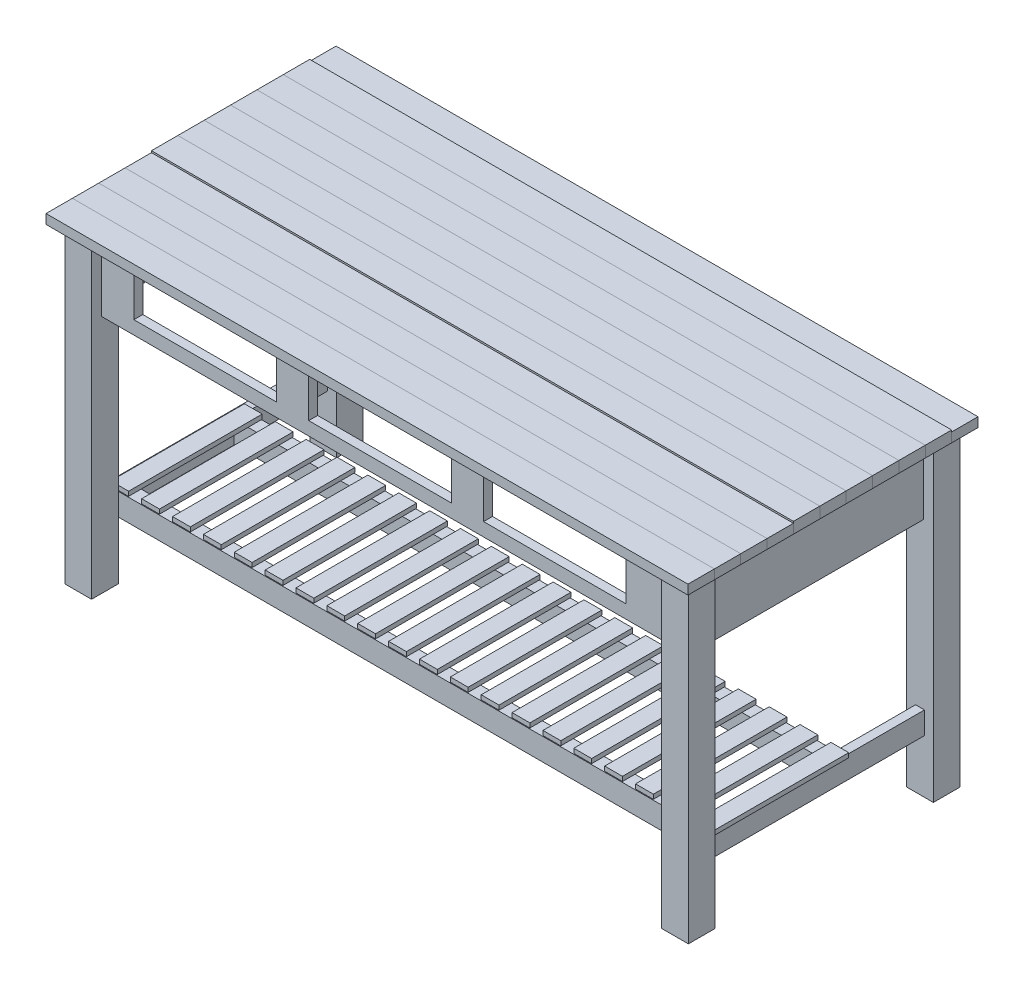
SolidWorks part; units mm, degrees
ref_plane "Default Plane" through (914.4, 26.9875, 137.455) normal (0, -1, 0) x (-1, 0, 0)
sketch3d "Bounding-Box_Cut-List-Item1"
  line L0 (0, 75.184, 0) -> (1830.3875, 75.184, 0) construction
  line L1 (1830.3875, 75.184, 0) -> (1830.3875, 0, 0) construction
  line L2 (1830.3875, 0, 0) -> (0, 0, 0) construction
  line L3 (0, 0, 0) -> (0, 75.184, 0) construction
  line L4 (0, 75.184, 26.9875) -> (1830.3875, 75.184, 26.9875) construction
  line L5 (1830.3875, 75.184, 26.9875) -> (1830.3875, 0, 26.9875) construction
  line L6 (1830.3875, 0, 26.9875) -> (0, 0, 26.9875) construction
  line L7 (0, 0, 26.9875) -> (0, 75.184, 26.9875) construction
  line L8 (0, 75.184, 0) -> (0, 75.184, 26.9875) construction
  line L9 (1830.3875, 75.184, 0) -> (1830.3875, 75.184, 26.9875) construction
  line L10 (1830.3875, 0, 0) -> (1830.3875, 0, 26.9875) construction
  line L11 (0, 0, 0) -> (0, 0, 26.9875) construction
ref_plane "Default Plane" through (889, 0, -663.915) normal (-1, 0, 0) x (0, 0, 1)
sketch3d "Bounding-Box_Cut-List-Item4"
  line L0 (76.2, 0, 0) -> (76.2, -887.4125, 0) construction
  line L1 (76.2, -887.4125, 0) -> (0, -887.4125, 0) construction
  line L2 (0, -887.4125, 0) -> (0, 0, 0) construction
  line L3 (0, 0, 0) -> (76.2, 0, 0) construction
  line L4 (76.2, 0, 76.2) -> (76.2, -887.4125, 76.2) construction
  line L5 (76.2, -887.4125, 76.2) -> (0, -887.4125, 76.2) construction
  line L6 (0, -887.4125, 76.2) -> (0, 0, 76.2) construction
  line L7 (0, 0, 76.2) -> (76.2, 0, 76.2) construction
  line L8 (76.2, 0, 0) -> (76.2, 0, 76.2) construction
  line L9 (76.2, -887.4125, 0) -> (76.2, -887.4125, 76.2) construction
  line L10 (0, -887.4125, 0) -> (0, -887.4125, 76.2) construction
  line L11 (0, 0, 0) -> (0, 0, 76.2) construction
ref_plane "Default Plane" through (863.6, -671.5125, -587.715) normal (-1, 0, 0) x (0, 0, 1)
sketch3d "Bounding-Box_Cut-List-Item5"
  line L0 (0, -63.5, 0) -> (622.3, -63.5, 0) construction
  line L1 (622.3, -63.5, 0) -> (622.3, 0, 0) construction
  line L2 (622.3, 0, 0) -> (0, 0, 0) construction
  line L3 (0, 0, 0) -> (0, -63.5, 0) construction
  line L4 (0, -63.5, 25.4) -> (622.3, -63.5, 25.4) construction
  line L5 (622.3, -63.5, 25.4) -> (622.3, 0, 25.4) construction
  line L6 (622.3, 0, 25.4) -> (0, 0, 25.4) construction
  line L7 (0, 0, 25.4) -> (0, -63.5, 25.4) construction
  line L8 (0, -63.5, 0) -> (0, -63.5, 25.4) construction
  line L9 (622.3, -63.5, 0) -> (622.3, -63.5, 25.4) construction
  line L10 (622.3, 0, 0) -> (622.3, 0, 25.4) construction
  line L11 (0, 0, 0) -> (0, 0, 25.4) construction
ref_plane "Default Plane" through (-812.8, 0, -663.915) normal (-1, 0, 0) x (0, 0, 1)
sketch3d "Bounding-Box_Cut-List-Item6"
  line L0 (0, 0, 0) -> (0, -887.4125, 0) construction
  line L1 (0, -887.4125, 0) -> (774.7, -887.4125, 0) construction
  line L2 (774.7, -887.4125, 0) -> (774.7, 0, 0) construction
  line L3 (774.7, 0, 0) -> (0, 0, 0) construction
  line L4 (0, 0, 76.2) -> (0, -887.4125, 76.2) construction
  line L5 (0, -887.4125, 76.2) -> (774.7, -887.4125, 76.2) construction
  line L6 (774.7, -887.4125, 76.2) -> (774.7, 0, 76.2) construction
  line L7 (774.7, 0, 76.2) -> (0, 0, 76.2) construction
  line L8 (0, 0, 0) -> (0, 0, 76.2) construction
  line L9 (0, -887.4125, 0) -> (0, -887.4125, 76.2) construction
  line L10 (774.7, -887.4125, 0) -> (774.7, -887.4125, 76.2) construction
  line L11 (774.7, 0, 0) -> (774.7, 0, 76.2) construction
material "Beech"
ref_plane "Front Plane" through (0, 0, 0) normal (0, 0, 1) x (1, 0, 0)
ref_plane "Top Plane" through (0, 0, 0) normal (0, 1, 0) x (1, 0, 0)
ref_plane "Right Plane" through (0, 0, 0) normal (1, 0, 0) x (0, 0, -1)
sketch "Sketch1" plane through (0, 0, 0) normal (0, 1, 0) x (1, 0, 0)
  line L0 (0, -450.3596) -> (0, 450.3596) construction
  line L1 (-915.9875, -62.271) -> (914.4, -62.271)
  line L2 (-915.9875, -62.271) -> (-915.9875, -137.455)
  line L3 (-915.9875, -137.455) -> (914.4, -137.455)
  line L4 (914.4, -62.271) -> (914.4, -137.455)
  line L6 (-915.9875, -62.271) -> (914.4, -62.271)
  line L7 (-915.9875, -62.271) -> (-915.9875, 12.913)
  line L8 (-915.9875, 12.913) -> (914.4, 12.913)
  line L9 (914.4, -62.271) -> (914.4, 12.913)
  line L10 (-915.9875, 12.913) -> (914.4, 12.913)
  line L11 (-915.9875, 12.913) -> (-915.9875, 88.097)
  line L12 (-915.9875, 88.097) -> (914.4, 88.097)
  line L13 (914.4, 12.913) -> (914.4, 88.097)
  line L14 (-915.9875, 88.097) -> (914.4, 88.097)
  line L15 (-915.9875, 88.097) -> (-915.9875, 163.281)
  line L16 (-915.9875, 163.281) -> (914.4, 163.281)
  line L17 (914.4, 88.097) -> (914.4, 163.281)
  line L18 (-915.9875, 163.281) -> (914.4, 163.281)
  line L19 (-915.9875, 163.281) -> (-915.9875, 238.465)
  line L20 (-915.9875, 238.465) -> (914.4, 238.465)
  line L21 (914.4, 163.281) -> (914.4, 238.465)
  line L22 (-915.9875, 238.465) -> (914.4, 238.465)
  line L23 (-915.9875, 238.465) -> (-915.9875, 313.649)
  line L24 (-915.9875, 313.649) -> (914.4, 313.649)
  line L25 (914.4, 238.465) -> (914.4, 313.649)
  line L26 (-915.9875, 313.649) -> (914.4, 313.649)
  line L27 (-915.9875, 313.649) -> (-915.9875, 388.833)
  line L28 (-915.9875, 388.833) -> (914.4, 388.833)
  line L29 (914.4, 313.649) -> (914.4, 388.833)
  line L30 (-915.9875, 388.833) -> (914.4, 388.833)
  line L31 (-915.9875, 388.833) -> (-915.9875, 464.017)
  line L32 (-915.9875, 464.017) -> (914.4, 464.017)
  line L33 (914.4, 388.833) -> (914.4, 464.017)
  line L34 (-915.9875, 464.017) -> (914.4, 464.017)
  line L35 (-915.9875, 464.017) -> (-915.9875, 539.201)
  line L36 (-915.9875, 539.201) -> (914.4, 539.201)
  line L37 (914.4, 464.017) -> (914.4, 539.201)
  line L38 (-915.9875, 539.201) -> (914.4, 539.201)
  line L39 (-915.9875, 539.201) -> (-915.9875, 614.385)
  line L40 (-915.9875, 614.385) -> (914.4, 614.385)
  line L41 (914.4, 539.201) -> (914.4, 614.385)
  line L42 (-915.9875, 614.385) -> (914.4, 614.385)
  line L44 (-915.9875, 614.385) -> (914.4, 614.385)
  line L46 (914.4, -137.455) -> (-915.9875, -137.455)
  line L47 (-915.9875, 614.385) -> (914.4, 614.385)
  line L48 (-915.9875, 614.385) -> (-915.9875, 689.569)
  line L49 (-915.9875, 689.569) -> (914.4, 689.569)
  line L50 (914.4, 614.385) -> (914.4, 689.569)
  dimension "D1" = 75.184
  dimension "D2" = 1830.3875
  dimension "D3" = 914.4
  dimension "D4" = 75.184
extrude "top1" add sketch "Sketch1" along normal blind 26.9875 contours L4 L1 L2 L3 region at (-0.7938, 0, 99.863)
extrude "top2" add sketch "Sketch1<9>" along normal blind 26.924 separate body contours L1 L9 L8 L7 region at (-0.7938, 0, 24.679)
sketch "Sketch1<9>" plane through (0, 0, 0) normal (0, 1, 0) x (1, 0, 0) same geometry as "Sketch1"
extrude "top3" add sketch "Sketch1<10>" along normal blind 26.924 separate body contours L8 L13 L12 L11 region at (-0.7938, 0, -50.505)
sketch "Sketch1<10>" plane through (0, 0, 0) normal (0, 1, 0) x (1, 0, 0) same geometry as "Sketch1"
extrude "top4" add sketch "Sketch1<11>" along normal blind 26.924 separate body contours L12 L17 L16 L15 region at (-0.7938, 0, -125.689)
sketch "Sketch1<11>" plane through (0, 0, 0) normal (0, 1, 0) x (1, 0, 0) same geometry as "Sketch1"
extrude "top5" add sketch "Sketch1<12>" along normal blind 31.75 separate body contours L16 L21 L20 L19 region at (-0.7938, 0, -200.873)
sketch "Sketch1<12>" plane through (0, 0, 0) normal (0, 1, 0) x (1, 0, 0) same geometry as "Sketch1"
extrude "top6" add sketch "Sketch1<13>" along normal blind 31.75 separate body contours L20 L25 L24 L23 region at (-0.7938, 0, -276.057)
sketch "Sketch1<13>" plane through (0, 0, 0) normal (0, 1, 0) x (1, 0, 0) same geometry as "Sketch1"
extrude "top7" add sketch "Sketch1<14>" along normal blind 31.75 separate body contours L24 L29 L28 L27 region at (-0.7938, 0, -351.241)
sketch "Sketch1<14>" plane through (0, 0, 0) normal (0, 1, 0) x (1, 0, 0) same geometry as "Sketch1"
extrude "top8" add sketch "Sketch1<15>" along normal blind 31.75 separate body contours L28 L33 L32 L31 region at (-0.7938, 0, -426.425)
sketch "Sketch1<15>" plane through (0, 0, 0) normal (0, 1, 0) x (1, 0, 0) same geometry as "Sketch1"
extrude "top9" add sketch "Sketch1<16>" along normal blind 31.75 separate body contours L32 L37 L36 L35 region at (-0.7938, 0, -501.609)
sketch "Sketch1<16>" plane through (0, 0, 0) normal (0, 1, 0) x (1, 0, 0) same geometry as "Sketch1"
extrude "top10" add sketch "Sketch1<17>" along normal blind 31.75 separate body contours L36 L41 L40 L39 region at (-0.7938, 0, -576.793)
sketch "Sketch1<17>" plane through (0, 0, 0) normal (0, 1, 0) x (1, 0, 0) same geometry as "Sketch1"
extrude "top11" add sketch "Sketch1<20>" along normal blind 26.924 separate body contours L3 L49 region at (-0.7938, 0, -651.977)
sketch "Sketch1<20>" plane through (0, 0, 0) normal (0, 1, 0) x (1, 0, 0) same geometry as "Sketch1"
sketch "Sketch2" plane through (0, 0, 0) normal (0, 1, 0) x (1, 0, 0)
  line L1 (-889, -110.785) -> (-812.8, -110.785)
  line L2 (-889, -110.785) -> (-889, -34.585)
  line L3 (-889, -34.585) -> (-812.8, -34.585)
  line L4 (-812.8, -110.785) -> (-812.8, -34.585)
  line L5 (-889, 587.715) -> (-812.8, 587.715)
  line L6 (-889, 587.715) -> (-889, 663.915)
  line L7 (-889, 663.915) -> (-812.8, 663.915)
  line L8 (-812.8, 587.715) -> (-812.8, 663.915)
  line L10 (0, -1000) -> (0, 49000) construction
  line L11 (812.8, 587.715) -> (812.8, 663.915)
  line L12 (889, 663.915) -> (812.8, 663.915)
  line L13 (889, 587.715) -> (889, 663.915)
  line L14 (889, 587.715) -> (812.8, 587.715)
  line L15 (812.8, -110.785) -> (812.8, -34.585)
  line L16 (889, -34.585) -> (812.8, -34.585)
  line L17 (889, -110.785) -> (889, -34.585)
  line L18 (889, -110.785) -> (812.8, -110.785)
  dimension "D1" = 76.2
  dimension "D2" = 76.2
  dimension "D3" = 622.3
  dimension "D4" = 812.8
  dimension "D5" = 812.8
extrude "table legs" add sketch "Sketch2" against normal blind 887.4125 separate body
ref_plane "Plane6" through (0, 0, -587.715) normal (0, 0, 1) x (1, 0, 0)
sketch "Sketch4" plane through (0, 0, -587.715) normal (0, 0, 1) x (1, 0, 0)
  line L0 (812.8, -887.4125) -> (889, -887.4125) construction
  line L1 (838.2, -671.5125) -> (863.6, -671.5125)
  line L2 (838.2, -671.5125) -> (838.2, -735.0125)
  line L3 (838.2, -735.0125) -> (863.6, -735.0125)
  line L4 (863.6, -671.5125) -> (863.6, -735.0125)
  line L5 (812.8, -887.4125) -> (812.8, 0) construction
  line L6 (889, -887.4125) -> (889, 0) construction
  point P4 (850.9, -887.4125)
  dimension "D1" = 152.4
  dimension "D2" = 25.4
  dimension "D3" = 63.5
  dimension "D4" = 25.4
extrude "stretcher width" add sketch "Sketch4" along normal up to surface (622.3 mm away) separate body up to face at (850.9, -443.7062, 34.585)
mirror "Mirror4" about plane through (0, 0, 0) normal (1, 0, 0) of "stretcher width"
ref_plane "Plane7" through (-838.2, 0, 0) normal (1, 0, 0) x (0, 0, -1)
sketch "Sketch5" plane through (-838.2, 0, 0) normal (1, 0, 0) x (0, 0, -1)
  line L1 (-34.585, -671.5125) -> (587.715, -671.5125) construction
  line L2 (-21.885, -671.5125) -> (16.215, -671.5125)
  line L3 (-21.885, -671.5125) -> (-21.885, -735.0125)
  line L4 (-21.885, -735.0125) -> (16.215, -735.0125)
  line L5 (16.215, -671.5125) -> (16.215, -735.0125)
  line L6 (-34.585, -735.0125) -> (587.715, -735.0125) construction
  line L7 (-34.585, -887.4125) -> (-34.585, 0) construction
  line L8 (587.715, -671.5125) -> (587.715, -735.0125) construction
  line L9 (359.115, -671.5125) -> (321.015, -671.5125)
  line L10 (359.115, -671.5125) -> (359.115, -735.0125)
  line L11 (359.115, -735.0125) -> (321.015, -735.0125)
  line L12 (321.015, -671.5125) -> (321.015, -735.0125)
  dimension "D1" = 12.7
  dimension "D2" = 38.1
  dimension "D3" = 228.6
  dimension "D4" = 38.1
extrude "stretcher length" add sketch "Sketch5" along normal up to surface (1676.4 mm away) separate body up to face at (838.2, -703.2625, -276.565)
ref_plane "Plane9" through (-812.8, 0, 0) normal (1, 0, 0) x (0, 0, -1)
sketch "Sketch7" plane through (-812.8, 0, 0) normal (1, 0, 0) x (0, 0, -1)
  line L0 (-110.785, 0) -> (-34.585, 0) construction
  line L1 (-82.21, 0) -> (-56.81, 0)
  line L2 (-82.21, 0) -> (-82.21, -203.2)
  line L3 (-82.21, -203.2) -> (-56.81, -203.2)
  line L4 (-56.81, 0) -> (-56.81, -203.2)
  line L6 (-34.585, -887.4125) -> (-34.585, 0) construction
  dimension "D1" = 22.225
  dimension "D2" = 25.4
  dimension "D3" = 203.2
extrude "front face plate" add sketch "Sketch7" along normal up to surface (1625.6 mm away) separate body up to face at (812.8, -443.7062, 72.685)
sketch "Sketch8" plane through (0, 0, -587.715) normal (0, 0, 1) x (1, 0, 0)
  line L0 (812.8, 0) -> (889, 0) construction
  line L1 (860.425, 0) -> (835.025, 0)
  line L2 (860.425, 0) -> (860.425, -203.2)
  line L3 (860.425, -203.2) -> (835.025, -203.2)
  line L4 (835.025, 0) -> (835.025, -203.2)
  line L6 (-889, 0) -> (-812.8, 0) construction
  line L7 (-860.425, 0) -> (-835.025, 0)
  line L8 (-860.425, 0) -> (-860.425, -203.2)
  line L9 (-860.425, -203.2) -> (-835.025, -203.2)
  line L10 (-835.025, 0) -> (-835.025, -203.2)
  line L12 (-812.8, -887.4125) -> (-812.8, 0) construction
  line L13 (812.8, -887.4125) -> (812.8, 0) construction
  dimension "D1" = 22.225
  dimension "D2" = 25.4
  dimension "D3" = 203.2
  dimension "D4" = 22.225
  dimension "D5" = 25.4
  dimension "D6" = 203.2
extrude "side face plates" add sketch "Sketch8" along normal up to surface (622.3 mm away) separate body up to face at (-850.9, -443.7062, 34.585)
ref_plane "Plane10" through (0, 0, -359.115) normal (0, 0, -1) x (-1, 0, 0)
sketch "Sketch9" plane through (0, 0, -359.115) normal (0, 0, -1) x (-1, 0, 0)
  line L0 (-788.2167, -669.1659) -> (-737.4167, -669.1659)
  line L1 (-876.2277, -669.1659) -> (-825.4277, -669.1659)
  line L2 (-876.2277, -669.1659) -> (-876.2277, -656.4659)
  line L3 (-876.2277, -656.4659) -> (-825.4277, -656.4659)
  line L4 (-825.4277, -669.1659) -> (-825.4277, -656.4659)
  line L5 (-788.2167, -669.1659) -> (-788.2167, -656.4659)
  line L6 (-788.2167, -656.4659) -> (-737.4167, -656.4659)
  line L7 (-737.4167, -669.1659) -> (-737.4167, -656.4659)
  line L8 (-700.2057, -669.1659) -> (-649.4057, -669.1659)
  line L9 (-700.2057, -669.1659) -> (-700.2057, -656.4659)
  line L10 (-700.2057, -656.4659) -> (-649.4057, -656.4659)
  line L11 (-649.4057, -669.1659) -> (-649.4057, -656.4659)
  line L12 (-612.1947, -669.1659) -> (-561.3947, -669.1659)
  line L13 (-612.1947, -669.1659) -> (-612.1947, -656.4659)
  line L14 (-612.1947, -656.4659) -> (-561.3947, -656.4659)
  line L15 (-561.3947, -669.1659) -> (-561.3947, -656.4659)
  line L16 (-524.1837, -669.1659) -> (-473.3837, -669.1659)
  line L17 (-524.1837, -669.1659) -> (-524.1837, -656.4659)
  line L18 (-524.1837, -656.4659) -> (-473.3837, -656.4659)
  line L19 (-473.3837, -669.1659) -> (-473.3837, -656.4659)
  line L20 (-436.1727, -669.1659) -> (-385.3727, -669.1659)
  line L21 (-436.1727, -669.1659) -> (-436.1727, -656.4659)
  line L22 (-436.1727, -656.4659) -> (-385.3727, -656.4659)
  line L23 (-385.3727, -669.1659) -> (-385.3727, -656.4659)
  line L24 (-348.1617, -669.1659) -> (-297.3617, -669.1659)
  line L25 (-348.1617, -669.1659) -> (-348.1617, -656.4659)
  line L26 (-348.1617, -656.4659) -> (-297.3617, -656.4659)
  line L27 (-297.3617, -669.1659) -> (-297.3617, -656.4659)
  line L28 (-260.1507, -669.1659) -> (-209.3507, -669.1659)
  line L29 (-260.1507, -669.1659) -> (-260.1507, -656.4659)
  line L30 (-260.1507, -656.4659) -> (-209.3507, -656.4659)
  line L31 (-209.3507, -669.1659) -> (-209.3507, -656.4659)
  line L32 (-172.1397, -669.1659) -> (-121.3397, -669.1659)
  line L33 (-172.1397, -669.1659) -> (-172.1397, -656.4659)
  line L34 (-172.1397, -656.4659) -> (-121.3397, -656.4659)
  line L35 (-121.3397, -669.1659) -> (-121.3397, -656.4659)
  line L36 (-84.1287, -669.1659) -> (-33.3287, -669.1659)
  line L37 (-84.1287, -669.1659) -> (-84.1287, -656.4659)
  line L38 (-84.1287, -656.4659) -> (-33.3287, -656.4659)
  line L39 (-33.3287, -669.1659) -> (-33.3287, -656.4659)
  line L40 (3.8823, -669.1659) -> (54.6823, -669.1659)
  line L41 (3.8823, -669.1659) -> (3.8823, -656.4659)
  line L42 (3.8823, -656.4659) -> (54.6823, -656.4659)
  line L43 (54.6823, -669.1659) -> (54.6823, -656.4659)
  line L44 (91.8933, -669.1659) -> (142.6933, -669.1659)
  line L45 (91.8933, -669.1659) -> (91.8933, -656.4659)
  line L46 (91.8933, -656.4659) -> (142.6933, -656.4659)
  line L47 (142.6933, -669.1659) -> (142.6933, -656.4659)
  line L48 (179.9043, -669.1659) -> (230.7043, -669.1659)
  line L49 (179.9043, -669.1659) -> (179.9043, -656.4659)
  line L50 (179.9043, -656.4659) -> (230.7043, -656.4659)
  line L51 (230.7043, -669.1659) -> (230.7043, -656.4659)
  line L52 (267.9153, -669.1659) -> (318.7153, -669.1659)
  line L53 (267.9153, -669.1659) -> (267.9153, -656.4659)
  line L54 (267.9153, -656.4659) -> (318.7153, -656.4659)
  line L55 (318.7153, -669.1659) -> (318.7153, -656.4659)
  line L56 (355.9263, -669.1659) -> (406.7263, -669.1659)
  line L57 (355.9263, -669.1659) -> (355.9263, -656.4659)
  line L58 (355.9263, -656.4659) -> (406.7263, -656.4659)
  line L59 (406.7263, -669.1659) -> (406.7263, -656.4659)
  line L60 (443.9373, -669.1659) -> (494.7373, -669.1659)
  line L61 (443.9373, -669.1659) -> (443.9373, -656.4659)
  line L62 (443.9373, -656.4659) -> (494.7373, -656.4659)
  line L63 (494.7373, -669.1659) -> (494.7373, -656.4659)
  line L64 (531.9483, -669.1659) -> (582.7483, -669.1659)
  line L65 (531.9483, -669.1659) -> (531.9483, -656.4659)
  line L66 (531.9483, -656.4659) -> (582.7483, -656.4659)
  line L67 (582.7483, -669.1659) -> (582.7483, -656.4659)
  line L68 (619.9593, -669.1659) -> (670.7593, -669.1659)
  line L69 (619.9593, -669.1659) -> (619.9593, -656.4659)
  line L70 (619.9593, -656.4659) -> (670.7593, -656.4659)
  line L71 (670.7593, -669.1659) -> (670.7593, -656.4659)
  line L72 (707.9703, -669.1659) -> (758.7703, -669.1659)
  line L73 (707.9703, -669.1659) -> (707.9703, -656.4659)
  line L74 (707.9703, -656.4659) -> (758.7703, -656.4659)
  line L75 (758.7703, -669.1659) -> (758.7703, -656.4659)
  line L76 (795.9813, -669.1659) -> (846.7813, -669.1659)
  line L77 (795.9813, -669.1659) -> (795.9813, -656.4659)
  line L78 (795.9813, -656.4659) -> (846.7813, -656.4659)
  line L79 (846.7813, -669.1659) -> (846.7813, -656.4659)
  dimension "D1" = 38.1
  dimension "D2" = 50.8
  dimension "D3" = 12.7
  dimension "D4" = 20
extrude "stretcher rack boards" add sketch "Sketch9" against normal up to surface (381 mm away) separate body up to face at (0, -703.2625, 21.885)
ref_plane "Plane11" through (0, 0, 82.21) normal (0, 0, 1) x (1, 0, 0)
sketch "Sketch10" plane through (0, 0, 82.21) normal (0, 0, 1) x (1, 0, 0)
  line L0 (-812.8, 0) -> (-812.8, -203.2) construction
  line L1 (-720.725, -38.1) -> (-314.325, -38.1)
  line L2 (-720.725, -38.1) -> (-720.725, -165.1)
  line L3 (-720.725, -165.1) -> (-314.325, -165.1)
  line L4 (-314.325, -38.1) -> (-314.325, -165.1)
  line L5 (812.8, 0) -> (-812.8, 0) construction
  line L6 (812.8, -203.2) -> (-812.8, -203.2) construction
  line L7 (-222.123, -38.1) -> (184.277, -38.1)
  line L8 (-222.123, -38.1) -> (-222.123, -165.1)
  line L9 (-222.123, -165.1) -> (184.277, -165.1)
  line L10 (184.277, -38.1) -> (184.277, -165.1)
  line L11 (276.479, -38.1) -> (682.879, -38.1)
  line L12 (276.479, -38.1) -> (276.479, -165.1)
  line L13 (276.479, -165.1) -> (682.879, -165.1)
  line L14 (682.879, -38.1) -> (682.879, -165.1)
  dimension "D1" = 92.075
  dimension "D2" = 38.1
  dimension "D3" = 38.1
  dimension "D4" = 406.4
  dimension "D5" = 3
extrude "drawer cut outs" cut sketch "Sketch10" against normal up to next (25.4 mm away)
ref_plane "Plane12" through (-812.8, 0, 0) normal (1, 0, 0) x (0, 0, -1)
sketch "Sketch11" plane through (-812.8, 0, 0) normal (1, 0, 0) x (0, 0, -1)
  line L0 (587.715, 0) -> (663.915, 0) construction
  line L1 (635.34, 0) -> (609.94, 0)
  line L2 (635.34, 0) -> (635.34, -101.6)
  line L3 (635.34, -101.6) -> (609.94, -101.6)
  line L4 (609.94, 0) -> (609.94, -101.6)
  line L6 (587.715, -887.4125) -> (587.715, 0) construction
  dimension "D1" = 22.225
  dimension "D2" = 101.6
  dimension "D3" = 25.4
extrude "back face plate" add sketch "Sketch11" along normal up to surface (1625.6 mm away) separate body up to face at (812.8, -443.7062, -625.815)
equation "\"table_thickness\"= \" 1 1 / 16\"in"
equation "\"D1@top1\"=\"table_thickness\""
equation "\"D1@top3\"=1.0625"
equation "\"D1@top4\"=1.0625"
equation "\"D1@top5\"=\"table_thickness\""
equation "\"D1@top6\"=\"table_thickness\""
equation "\"D1@top7\"=\"table_thickness\""
equation "\"D1@top8\"=\"table_thickness\""
equation "\"D1@top9\"=\"table_thickness\""
equation "\"D1@top10\"=\"table_thickness\""
equation "\"D1@top11\"=1.0625"
